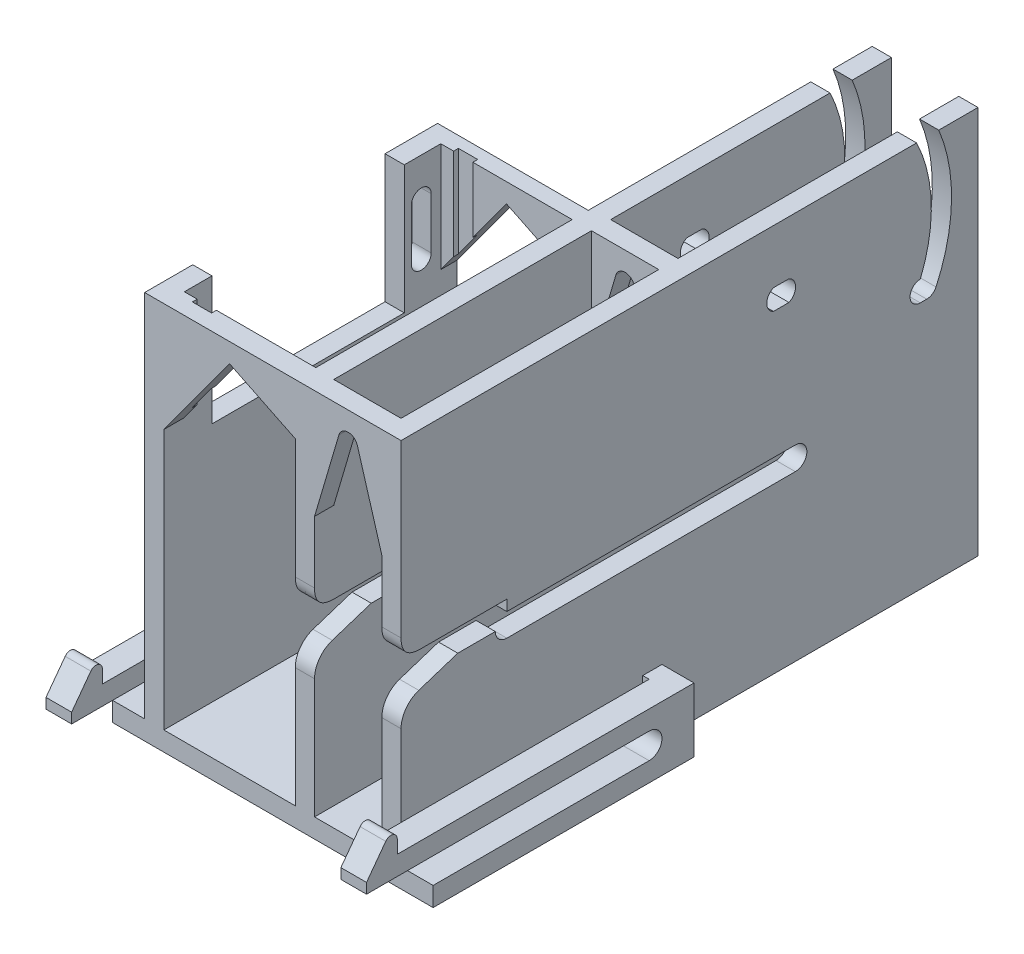
SolidWorks part; units mm, degrees
ref_plane "Front Plane" through (0, 0, 0) normal (0, 0, 1) x (1, 0, 0)
ref_plane "Top Plane" through (0, 0, 0) normal (0, 1, 0) x (1, 0, 0)
ref_plane "Right Plane" through (0, 0, 0) normal (1, 0, 0) x (0, 0, -1)
sketch "Sketch1" plane through (0, 0, 0) normal (0, 0, 1) x (1, 0, 0)
  line L0 (-28.75, 32.8115) -> (-8.25, 32.8115)
  line L1 (-31.75, 32.8115) -> (-28.75, 32.8115)
  line L2 (-31.75, 32.8115) -> (-31.75, -27.7885)
  line L3 (-31.75, -27.7885) -> (-28.75, -27.7885)
  line L4 (-28.75, 32.8115) -> (-28.75, -27.7885)
  line L5 (-31.75, -24.7885) -> (8.25, -24.7885)
  line L6 (-31.75, -24.7885) -> (-31.75, -27.7885)
  line L7 (-31.75, -27.7885) -> (8.25, -27.7885)
  line L8 (8.25, -24.7885) -> (8.25, -27.7885)
  line L9 (8.25, -27.7885) -> (5.25, -27.7885)
  line L10 (8.25, -27.7885) -> (8.25, 32.8115)
  line L11 (8.25, 32.8115) -> (5.25, 32.8115)
  line L12 (5.25, -27.7885) -> (5.25, 32.8115)
  line L13 (-8.25, -27.7885) -> (-5.25, -27.7885)
  line L14 (-8.25, -27.7885) -> (-8.25, 32.8115)
  line L15 (-8.25, 32.8115) -> (-5.25, 32.8115)
  line L16 (-5.25, -27.7885) -> (-5.25, 32.8115)
  line L17 (-5.25, 5.9115) -> (5.25, 5.9115)
  line L18 (-5.25, 5.9115) -> (-5.25, 3.9115)
  line L19 (-5.25, 3.9115) -> (5.25, 3.9115)
  line L20 (5.25, 5.9115) -> (5.25, 3.9115)
  line L21 (-28.75, 15.8115) -> (-18.5, 29.8115)
  line L22 (-18.5, 29.8115) -> (-8.25, 24.8115)
  point P22 (-18.5, 32.8115)
  point P31 (0, 3.9115)
  dimension "D1" = 3
  dimension "D2" = 3
  dimension "D3" = 3
  dimension "D4" = 20.5
  dimension "D5" = 10.5
  dimension "D6" = 2
  dimension "D7" = 28.7
  dimension "D8" = 60.6
  dimension "D9" = 8
  dimension "D10" = 17
extrude "Main Extrude" add sketch "Sketch1" along normal blind 90 contours L21 L22 L14 L0 L4 | L2 L5 L4 L1 | L7 L14 L5 L4 | L5 L2 L3 L4 | L7 L16 L5 L14 | L5 L16 L15 L14 | L16 L7 L12 L5 | L12 L7 L8 L5 | L12 L5 L10 L11 | L16 L19 L12 L17 region at (-30.25, 4.0115, 0) region at (-20.4839, 28.0158, 0) region at (-6.75, 4.0115, 0) region at (-30.25, -26.2885, 0) region at (-18.5, -26.2885, 0) region at (-6.75, -26.2885, 0) region at (0, 4.9115, 0) region at (0, -26.2885, 0) region at (6.75, 4.0115, 0) region at (6.75, -26.2885, 0)
sketch "Sketch2" plane through (8.25, 0, 0) normal (1, 0, 0) x (0, 0, -1)
  line L0 (-73.5, -0.3385) -> (-28.5, -0.3385) construction
  line L1 (-73.5, 1.4615) -> (-28.5, 1.4615)
  line L2 (-73.5, -2.1385) -> (-28.5, -2.1385)
  line L3 (-30.9089, 24.4115) -> (-29.4911, 24.4115)
  line L4 (-30.9089, 21.2115) -> (-29.4911, 21.2115)
  line L5 (0, -27.7885) -> (0, 32.8115) construction
  line L6 (-90, 32.8115) -> (0, 32.8115) construction
  line L7 (-90, -27.7885) -> (0, -27.7885) construction
  line L8 (-90, -27.7885) -> (-90, 32.8115) construction
  line L9 (-5, 32.8115) -> (-5, -27.7885) construction
  line L10 (-90, 32.8115) -> (0, 32.8115) construction
  line L11 (-90, -27.7885) -> (0, -27.7885) construction
  line L12 (-90, 32.8115) -> (-90, -27.7885) construction
  line L13 (-31.9089, 24.4115) -> (-30.4911, 24.4115)
  line L14 (-31.9089, 21.2115) -> (-30.4911, 21.2115)
  line L15 (-30.9089, 24.4115) -> (-30.4911, 24.4115)
  line L16 (-30.9089, 21.2115) -> (-30.4911, 21.2115)
  line L17 (-8, 10.9115) -> (-9, 10.9115)
  line L18 (-8, 14.1115) -> (-9, 14.1115)
  line L19 (-6.1209, 32.8115) -> (-7.8633, 32.8115)
  line L20 (-73.5, 3.1365) -> (-90, 3.1365)
  line L21 (-73.5, 3.1365) -> (-73.5, -0.3385)
  line L22 (-73.5, -0.3385) -> (-90, -0.3385)
  line L23 (-90, 3.1365) -> (-90, -0.3385)
  line L24 (-7.8633, 32.8115) -> (-9.5813, 32.8115)
  arc A0 (-8, 10.9115) -> (-8, 14.1115) centre (-8, 12.5115) ccw
  arc A2 (-73.5, 1.4615) -> (-73.5, -2.1385) centre (-73.5, -0.3385) ccw
  arc A3 (-28.5, -2.1385) -> (-28.5, 1.4615) centre (-28.5, -0.3385) ccw
  arc A4 (-29.4911, 21.2115) -> (-29.4911, 24.4115) centre (-30.2, 22.8115) ccw
  arc A5 (-9, 14.1115) -> (-9, 10.9115) centre (-9, 12.5115) ccw
  arc A6 (-31.9089, 24.4115) -> (-31.9089, 21.2115) centre (-31.2, 22.8115) ccw
  arc A7 (-7.3744, 13.9841) -> (-7.8633, 32.8115) centre (-30.2, 22.8115) ccw
  arc A8 (-6.5486, 11.8381) -> (-6.1209, 32.8115) centre (-30.2, 22.8115) ccw
  arc A10 (-8, 10.9115) -> (-8, 14.1115) centre (-8, 12.5115) ccw
  arc A12 (-9, 14.1115) -> (-9.5813, 32.8115) centre (-30.2, 22.8115) ccw
  point P6 (-51, -0.3385)
  point P61 (-30.2, 24.4115)
  line M10 (0, 32.8115) -> (-90, 32.8115)
  line M11 (-90, 32.8115) -> (-90, -27.7885)
  dimension "D3" = 3.2
  dimension "D4" = 1.4177
  dimension "D6" = 8
  dimension "D9" = 1.8
  dimension "D10" = 27.45
  dimension "D11" = 16.5
  dimension "D1" = 22.2
  dimension "D2" = 10.3
  dimension "D5" = 3.2
  dimension "D7" = 10
  dimension "D8" = 45
  dimension "D12" = 85
  dimension "D13" = 22.2
  dimension "D14" = 4
  dimension "D15" = 3.475
  dimension "D16" = 16.5
extrude "Switch/Lever Holes" cut sketch "Sketch2" along normal up to surface from surface contours A2 L21 L20 L22 M11 | L21 A2 | L2 A3 L1 L21 | L13 A6 L14 L4 A4 L3 | L18 A5 L17 A0 | A12 L18 A0 A7 M10 | A0 A8 A7 M10 region at (8.25, 23.4905, 7.1621) region at (8.25, 1.4442, 82.0977) region at (8.25, -0.35, 50.651) region at (8.25, 0.4254, 74.2639) region at (8.25, 23.0854, 5.5723) region at (8.25, 12.5115, 8.5) region at (8.25, 22.8115, 30.7) up to face at (8.25, 2.5115, 45) starting at face at (-8.25, 0.0115, 45)
sketch "Sketch3" plane through (-31.75, 0, 0) normal (-1, 0, 0) x (0, 0, 1)
  line L0 (90, 32.8115) -> (0, 32.8115) construction
  line L1 (52.5, 32.8115) -> (82.5, 32.8115)
  line L2 (52.5, 32.8115) -> (52.5, 12.8115)
  line L3 (52.5, 12.8115) -> (82.5, 12.8115)
  line L4 (82.5, 32.8115) -> (82.5, 12.8115)
  line L5 (49.85, 26.8115) -> (49.85, 18.8115) construction
  line L6 (51.4, 26.8115) -> (51.4, 18.8115)
  line L7 (48.3, 26.8115) -> (48.3, 18.8115)
  line L8 (85.15, 26.8115) -> (85.15, 18.8115) construction
  line L9 (86.7, 26.8115) -> (86.7, 18.8115)
  line L10 (83.6, 26.8115) -> (83.6, 18.8115)
  line L11 (90, 32.8115) -> (90, -27.7885) construction
  line L13 (44.3, 32.8115) -> (0, 32.8115)
  line L14 (44.3, 32.8115) -> (44.3, -27.7885)
  line L15 (44.3, -27.7885) -> (0, -27.7885)
  line L16 (0, 32.8115) -> (0, -27.7885)
  arc A0 (51.4, 26.8115) -> (48.3, 26.8115) centre (49.85, 26.8115) ccw
  arc A1 (48.3, 18.8115) -> (51.4, 18.8115) centre (49.85, 18.8115) ccw
  arc A2 (86.7, 26.8115) -> (83.6, 26.8115) centre (85.15, 26.8115) ccw
  arc A3 (83.6, 18.8115) -> (86.7, 18.8115) centre (85.15, 18.8115) ccw
  point P8 (49.85, 22.8115)
  point P13 (85.15, 22.8115)
  dimension "D5" = 1.55
  dimension "D7" = 6
  dimension "D8" = 6
  dimension "D1" = 20
  dimension "D2" = 30
  dimension "D3" = 7.5
  dimension "D4" = 35.3
  dimension "D6" = 1.1
  dimension "D9" = 4
extrude "Servo Mount Slots" cut sketch "Sketch3" against normal up to surface (23.5 mm away) up to face at (-8.25, 22.8115, 30.7)
sketch "Sketch4" plane through (0, 0, 51.4) normal (0, 0, -1) x (-1, 0, 0)
  line L1 (8.25, 32.8115) -> (28.75, 32.8115)
  line L2 (8.25, 32.8115) -> (8.25, 24.8115)
  line L3 (8.25, 24.8115) -> (28.75, 24.8115)
  line L4 (28.75, 32.8115) -> (28.75, 24.8115)
  line L5 (18.5, 29.8115) -> (8.25, 24.8115) construction
  line L6 (28.75, 18.8115) -> (28.75, 15.8115) construction
extrude "Servo Hole Expansion" cut sketch "Sketch4" against normal up to surface (32.2 mm away) up to face at (-9.6167, 26.1448, 83.6)
sketch "Sketch5" plane through (0, 32.8115, 0) normal (0, 1, 0) x (1, 0, 0)
  line L0 (-28.75, -82.5) -> (-28.75, -52.5) construction
  line L1 (-8.25, -46.8) -> (-28.75, -46.8)
  line L2 (-8.25, -46.8) -> (-8.25, -86.8)
  line L3 (-8.25, -86.8) -> (-28.75, -86.8)
  line L4 (-28.75, -46.8) -> (-28.75, -86.8)
  line L5 (-8.25, -44.3) -> (-31.75, -44.3) construction
  line L7 (-8.25, -51.4) -> (-8.25, -83.6) construction
  line L8 (-5.25, -90) -> (-5.25, 0) construction
  line L9 (5.25, 0) -> (-5.25, 0)
  line L10 (5.25, 0) -> (5.25, -12)
  line L11 (5.25, -12) -> (-5.25, -12)
  line L12 (-5.25, 0) -> (-5.25, -12)
  line L13 (5.25, -90) -> (5.25, -9.5813) construction
  line L14 (5.25, -90) -> (-5.25, -90)
  line L15 (5.25, -90) -> (5.25, -22)
  line L16 (5.25, -22) -> (-5.25, -22)
  line L17 (-5.25, -90) -> (-5.25, -22)
  line L18 (5.25, -90) -> (5.25, 0) construction
  line L19 (-5.25, -90) -> (5.25, -90) construction
  line L20 (8.25, 0) -> (5.25, 0) construction
  dimension "D1" = 40
  dimension "D2" = 2.5
  dimension "D3" = 10
  dimension "D4" = 12
extrude "Servo Hole Expansion 2" cut sketch "Sketch5" against normal up to surface (57.6 mm away) up to face at (-18.5, -24.7885, 67.15)
sketch "Sketch6" plane through (-31.75, 0, 0) normal (-1, 0, 0) x (0, 0, 1)
  line L0 (90, -27.7885) -> (44.3, -27.7885) construction
  line L1 (49.3, -27.7885) -> (90, -27.7885)
  line L2 (49.3, -27.7885) -> (49.3, -17.7885)
  line L3 (49.3, -17.7885) -> (100.388, -17.7885)
  line L5 (56.3, -22.7885) -> (100.388, -22.7885) construction
  line L6 (56.3, -20.7885) -> (100.388, -20.7885)
  line L7 (56.3, -24.7885) -> (100.388, -24.7885)
  line L8 (90, -24.7885) -> (90, -27.7885)
  line L9 (100.388, -19.1885) -> (97.3916, -15.143)
  line L10 (95.588, -15.7382) -> (95.588, -17.7885)
  line L11 (44.3, -27.7885) -> (44.3, 32.8115) construction
  line L12 (100.388, -20.7885) -> (100.388, -17.7885)
  line L13 (90, 32.8115) -> (90, -27.7885) construction
  arc A0 (56.3, -20.7885) -> (56.3, -24.7885) centre (56.3, -22.7885) ccw
  arc A1 (100.388, -24.7885) -> (100.388, -20.7885) centre (100.388, -22.7885) ccw
  arc A2 (97.3916, -15.143) -> (95.588, -15.7382) centre (96.588, -15.7382) ccw
  point P8 (78.344, -22.7885)
  point P19 (49.3, -22.7885)
  point P20 (54.3, -22.7885)
  point P29 (96.2746, -14.7885)
  line M23 (44.3, -27.7885) -> (90, -27.7885)
  line M24 (90, -27.7885) -> (90, 32.8115)
  dimension "D6" = 2
  dimension "D5" = 1.6
  dimension "D9" = 1
  dimension "D1" = 5
  dimension "D2" = 5
  dimension "D3" = 4.8
  dimension "D4" = 3
  dimension "D7" = 6
  dimension "D8" = 5.588
extrude "Tab1" add sketch "Sketch6" along normal blind 5 contours A0 L6 L3 L2 L7 M24 M23 | L6 L12 L9 L3 M24 | L9 A2 L10 L3 region at (-31.75, -22.7885, 49.7191) region at (-31.75, -19.3132, 95.0784) region at (-31.75, -16.5313, 97.0175)
extrude "Tab2" add sketch "Sketch6<4>" against normal blind 5 from surface contours A0 L6 L3 L2 L7 M24 M23 | L6 L12 L9 L3 M24 | L9 A2 L10 L3 region at (-31.75, -22.7885, 49.7191) region at (-31.75, -19.3132, 95.0784) region at (-31.75, -16.5313, 97.0175) starting at face at (8.25, 22.8115, 30.7)
sketch "Sketch6<4>" plane through (-31.75, 0, 0) normal (-1, 0, 0) x (0, 0, 1) same geometry as "Sketch6"
sketch "Sketch7" plane through (0, 32.8115, 0) normal (0, 1, 0) x (1, 0, 0)
  line L0 (-31.75, -49.3) -> (-31.75, -90) construction
  line L1 (-31.75, -52.3) -> (-32.75, -52.3)
  line L2 (-31.75, -52.3) -> (-31.75, -100.388)
  line L3 (-31.75, -100.388) -> (-32.75, -100.388)
  line L4 (-32.75, -52.3) -> (-32.75, -100.388)
  line L5 (8.25, -90) -> (8.25, -9.5813) construction
  line L6 (8.25, -52.3) -> (9.25, -52.3)
  line L7 (8.25, -52.3) -> (8.25, -100.388)
  line L8 (8.25, -100.388) -> (9.25, -100.388)
  line L9 (9.25, -52.3) -> (9.25, -100.388)
  line L11 (-36.75, -49.3) -> (-31.75, -49.3) construction
  line L14 (-31.75, -90) -> (-31.75, -95.588) construction
  line L15 (8.25, -90) -> (8.25, -95.588) construction
  dimension "D1" = 1
  dimension "D2" = 3
extrude "Tab Spacer" cut sketch "Sketch7" against normal up to surface (57.6 mm away) up to face at (-18.5, -24.7885, 67.15)
sketch "Sketch8" plane through (-5.25, 0, 0) normal (1, 0, 0) x (0, 0, -1)
  line L0 (-22, 5.9115) -> (-22, 3.9115)
  line L2 (-22, 3.9115) -> (-17, 3.9115)
  line L3 (-22, 3.9115) -> (-12, 3.9115) construction
  arc A0 (-17, 3.9115) -> (-22, 5.9115) centre (-17, 11.1615) cw
extrude "Lever Shelf" cut sketch "Sketch8" along normal up to surface (10.5 mm away) up to face at (5.25, 7.3953, 42.0495)
sketch "Sketch10" plane through (0, 0, 0) normal (0, 0, -1) x (-1, 0, 0)
  line L1 (-5.25, 2.4615) -> (5.25, 2.4615)
  line L2 (-5.25, 2.4615) -> (-5.25, 5.9115)
  line L3 (-5.25, 5.9115) -> (5.25, 5.9115)
  line L4 (5.25, 2.4615) -> (5.25, 5.9115)
  line L5 (5.25, 5.9115) -> (-5.25, 5.9115) construction
  point P7 (0, 5.9115)
  point P10 (0, 5.9115)
  dimension "D1" = 10.5
  dimension "D3" = 1
extrude "Cut-Extrude2" cut sketch "Sketch10" against normal blind 45
sketch "Sketch11" plane through (0, 0, 90) normal (0, 0, 1) x (1, 0, 0)
  line L0 (-5.25, 32.8115) -> (5.25, 32.8115)
  line L1 (5.25, 32.8115) -> (5.25, 15.8115)
  line L2 (5.25, 3.1365) -> (5.25, 32.8115) construction
  line L5 (-5.25, 3.1365) -> (-5.25, 32.8115) construction
  line L6 (-5.25, 15.8115) -> (-5.25, 32.8115)
  line L7 (-5.25, 15.8115) -> (-1.4387, 28.7357)
  line L8 (1.4387, 28.7357) -> (5.25, 15.8115)
  arc A0 (-1.4387, 28.7357) -> (1.4387, 28.7357) centre (0, 28.3115) cw
  point P13 (0, 29.8115)
  point P18 (0, 32.8115)
  dimension "D1" = 1.5
extrude "Boss-Extrude1" add sketch "Sketch11" against normal blind 3
extrude "Boss-Extrude2" add sketch "Sketch11<2>" against normal blind 3 from surface starting at face at (-18.5, 27.2115, 46.8)
sketch "Sketch11<2>" plane through (0, 0, 90) normal (0, 0, 1) x (1, 0, 0) same geometry as "Sketch11"
fillet "Fillet1" radius 3 4 edges at (6.75, -0.3385, 90) (-6.75, -0.3385, 90) (-6.75, 3.1365, 90) (6.75, 3.1365, 90) conic rho 0.5
sketch "Sketch12" plane through (0, 32.8115, 0) normal (0, 1, 0) x (1, 0, 0)
  line L1 (-28.75, -86.8) -> (-8.25, -86.8) construction
  line L2 (-23.75, -86.8) -> (-26.75, -86.8)
  line L3 (-23.75, -86.8) -> (-23.75, -87.55)
  line L4 (-23.75, -87.55) -> (-26.75, -87.55)
  line L5 (-26.75, -86.8) -> (-26.75, -87.55)
  line L6 (-8.25, -46.8) -> (-28.75, -46.8) construction
  line L7 (-23.75, -46.8) -> (-26.75, -46.8)
  line L8 (-23.75, -46.8) -> (-23.75, -46.05)
  line L9 (-23.75, -46.05) -> (-26.75, -46.05)
  line L10 (-26.75, -46.8) -> (-26.75, -46.05)
  line L11 (-31.75, -52.3) -> (-31.75, -90) construction
  dimension "D1" = 0.75
  dimension "D2" = 8
  dimension "D3" = 3
extrude "Cut-Extrude3" cut sketch "Sketch12" against normal up to surface (10.1707 mm away) up to face at (-23.625, 22.8115, 88.4)
sketch "Sketch13" plane through (8.25, 0, 0) normal (1, 0, 0) x (0, 0, -1)
  line L0 (-81.15, -0.3385) -> (-90, -0.3385)
  line L3 (-75.3, -0.3385) -> (-87, -0.3385) construction
  line L4 (-90, 15.8115) -> (-90, -24.7885) construction
  line L5 (-90, -0.3385) -> (-90, -3.2135)
  line L6 (-90, -24.7885) -> (-90, -3.3385) construction
  line L7 (-90, -3.2135) -> (-81.15, -0.3385)
  line L8 (-73.5, 3.1365) -> (-87, 3.1365) construction
  dimension "D1" = 6.35
extrude "Cut-Extrude4" cut sketch "Sketch13" against normal up to surface (16.5 mm away) up to face at (-8.25, 7.9337, 49.5675)
fillet "Fillet2" radius 4 2 edges
